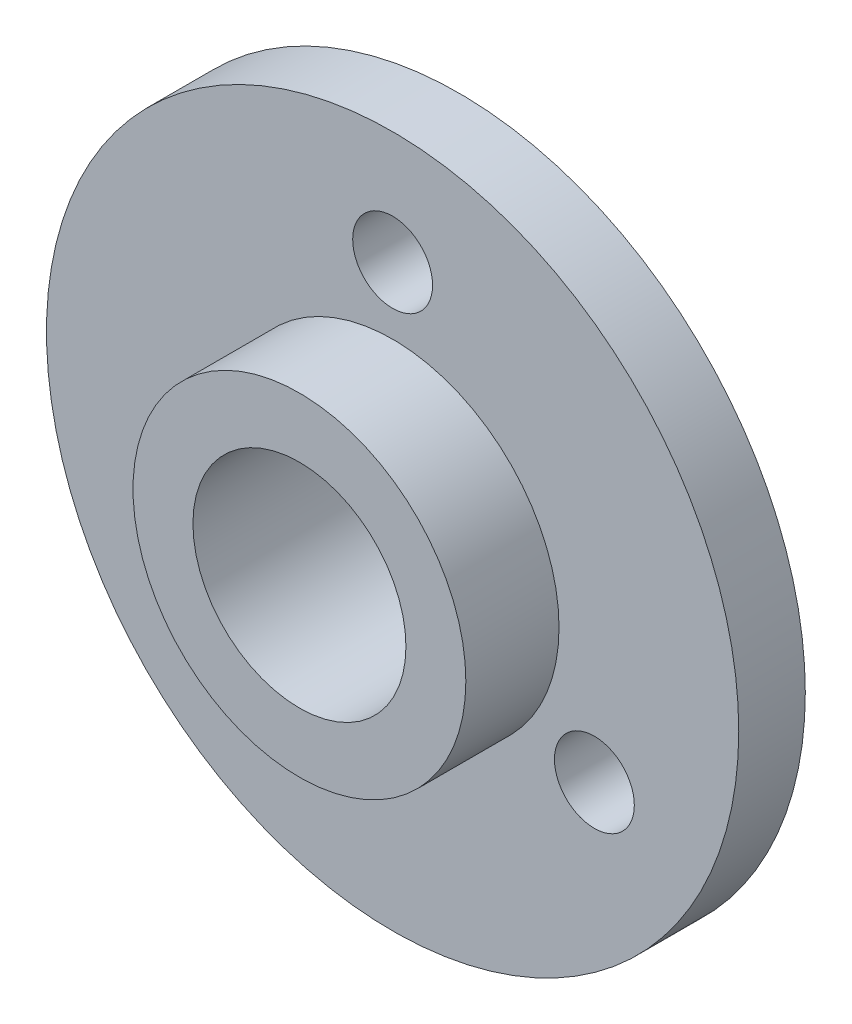
SolidWorks part; units mm, degrees
material "AISI 1020"
ref_plane "Front Plane" through (0, 0, 0) normal (0, 0, 1) x (1, 0, 0)
ref_plane "Top Plane" through (0, 0, 0) normal (0, 1, 0) x (1, 0, 0)
ref_plane "Right Plane" through (0, 0, 0) normal (1, 0, 0) x (0, 0, -1)
sketch "Sketch1" plane through (0, 0, 0) normal (0, 0, 1) x (1, 0, 0)
  circle A0 centre (0, 0) radius 12.5
  circle A1 centre (0, 0) radius 8
  circle A2 centre (0, 0) radius 26
  dimension "D1" = 52
  dimension "D2" = 25
  dimension "D3" = 16
extrude "Boss-Extrude1" add sketch "Sketch1" along normal blind 5 contours A2 A0 region at (-25.2646, 0, 0)
extrude "Boss-Extrude2" add sketch "Sketch1<3>" along normal blind 12 contours A0 A1 region at (-12.1464, 0, 0)
sketch "Sketch1<3>" plane through (0, 0, 0) normal (0, 0, 1) x (1, 0, 0) same geometry as "Sketch1"
sketch "Sketch2" plane through (0, 0, 0) normal (0, 0, -1) x (-1, 0, 0)
  line L0 (0, 24.2373) -> (0, -19.511) construction
  line L1 (-20.467, 0) -> (18.932, 0) construction
  circle A0 centre (0, 17.5) radius 3
  circle A1 centre (15.1554, -8.75) radius 3
  circle A2 centre (-15.1554, -8.75) radius 3
  circle A3 centre (0, 0) radius 17.5 construction
  point P13 (0, 0)
  dimension "D2" = 6
  dimension "D3" = 35
  dimension "D1" = 3
extrude "Cut-Extrude1" cut sketch "Sketch2" against normal through all
